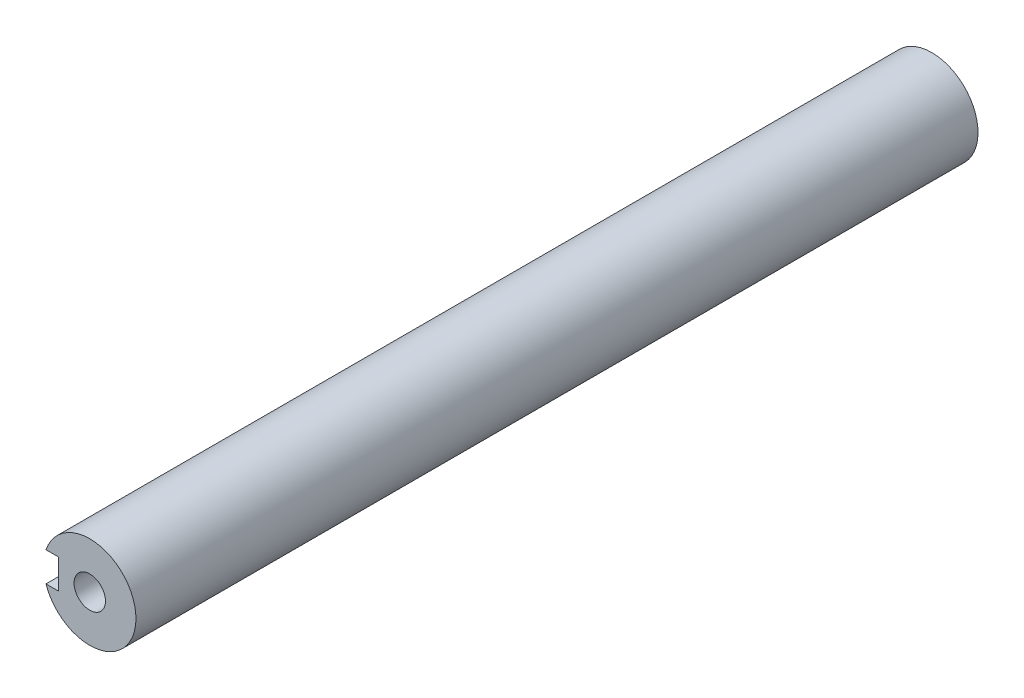
SolidWorks part; units mm, degrees
material "AISI 1020"
ref_plane "Спереди" through (0, 0, 0) normal (0, 0, 1) x (1, 0, 0)
ref_plane "Сверху" through (0, 0, 0) normal (0, 1, 0) x (1, 0, 0)
ref_plane "Справа" through (0, 0, 0) normal (1, 0, 0) x (0, 0, -1)
sketch "Эскиз1" plane through (0, 0, 0) normal (0, 0, 1) x (1, 0, 0)
  circle A1 centre (0.1925, -155.8076) radius 12.5
  arc A2 (-11.6503, -159.8076) -> (-11.6503, -151.8076) centre (0.1925, -155.8076) ccw construction
extrude "Бобышка-Вытянуть1" add sketch "Эскиз1" against normal offset from surface (227.9 mm away) 1.5 from offset 1.5 offset against normal yes
ref_point "Точка1"
ref_point "Точка2"
hole_wizard "Отверстие обработанное метчиком M101" positions "Эскиз2" profile "Эскиз3" tap size "M10" standard "ISO"
sketch "Эскиз2" plane through (0, 0, -1.5) normal (0, 0, 1) x (1, 0, 0)
  point P0 (0.1925, -155.8076)
sketch "Эскиз3" plane through (0.1925, -155.8076, -1.5) normal (1, 0, 0) x (0, -1, 0)
  line L0 (0, 0) -> (0, 32.5537)
  line L1 (0, 32.5537) -> (4.25, 30)
  line L2 (4.25, 30) -> (4.25, 0)
  line L5 (4.25, 0) -> (0, 0)
  line L10 (0, 32.5537) -> (-4.25, 30) construction
  line L11 (0, -6.35) -> (0, 107.95) construction
  dimension "Диаметр сверла" = 8.5
  dimension "Глубина сверла" = 30
  dimension "Угол заточки сверла" = 118
cosmetic thread "Отверстие резьбы1" parameters "D1"=25, "D2"=10
hole_wizard "Отверстие обработанное метчиком M102" positions "Эскиз4" profile "Эскиз5" tap size "M10" standard "ISO"
sketch "Эскиз4" plane through (0, 0, -229.4) normal (0, 0, -1) x (-1, 0, 0)
  point P0 (-0.1925, -155.8076)
sketch "Эскиз5" plane through (0.1925, -155.8076, -229.4) normal (1, 0, 0) x (0, 1, 0)
  line L0 (0, 0) -> (0, 35.0537)
  line L1 (0, 35.0537) -> (4.25, 32.5)
  line L2 (4.25, 32.5) -> (4.25, 0)
  line L5 (4.25, 0) -> (0, 0)
  line L10 (0, 35.0537) -> (-4.25, 32.5) construction
  line L11 (0, -6.35) -> (0, 107.95) construction
  dimension "Диаметр сверла" = 8.5
  dimension "Глубина сверла" = 32.5
  dimension "Угол заточки сверла" = 118
cosmetic thread "Отверстие резьбы2" parameters "D1"=25, "D2"=10
sketch "Эскиз6" plane through (0, 0, -1.5) normal (0, 0, 1) x (1, 0, 0)
  line L1 (-16.3075, -159.8076) -> (-8.3075, -159.8076)
  line L2 (-16.3075, -159.8076) -> (-16.3075, -151.8076)
  line L3 (-16.3075, -151.8076) -> (-8.3075, -151.8076)
  line L4 (-8.3075, -159.8076) -> (-8.3075, -151.8076)
  line L5 (-16.3075, -159.8076) -> (-8.3075, -151.8076) construction
  line L6 (-16.3075, -151.8076) -> (-8.3075, -159.8076) construction
  circle A0 centre (0.1925, -155.8076) radius 12.5 construction
  point P0 (-12.3075, -155.8076)
  dimension "D1" = 8
extrude "Вырез-Вытянуть1" cut sketch "Эскиз6" against normal blind 30
